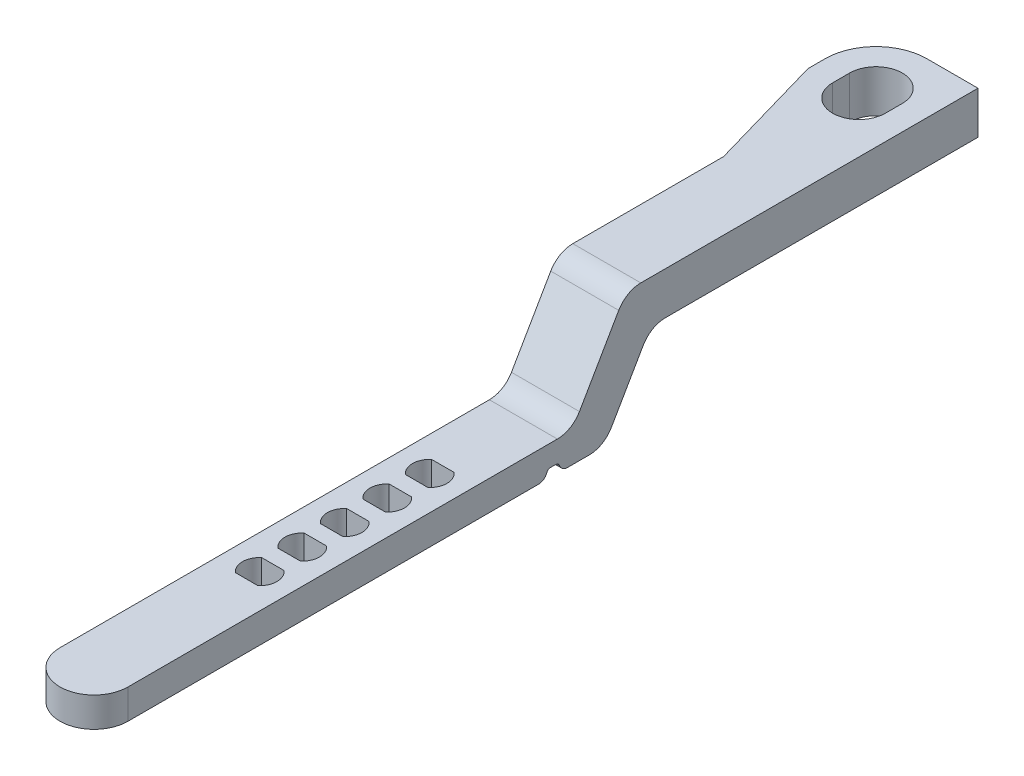
SolidWorks part; units mm, degrees
ref_plane "Front Plane" through (0, 0, 0) normal (0, 0, 1) x (1, 0, 0)
ref_plane "Top Plane" through (0, 0, 0) normal (0, 1, 0) x (1, 0, 0)
ref_plane "Right Plane" through (0, 0, 0) normal (1, 0, 0) x (0, 0, -1)
other "Configuration Table"
sketch "Sketch1" plane through (0, 0, 0) normal (0, 0, 1) x (1, 0, 0)
  line L1 (-4, 1.75) -> (4, 1.75)
  line L2 (-4, 1.75) -> (-4, -1.75)
  line L3 (-4, -1.75) -> (4, -1.75)
  line L4 (4, 1.75) -> (4, -1.75)
  line L5 (-4, 1.75) -> (4, -1.75) construction
  line L6 (-4, -1.75) -> (4, 1.75) construction
  point P0 (0, 0)
  dimension "D1" = 3.5
  dimension "D2" = 8
extrude "Base" add sketch "Sketch1" along normal blind 50
ref_plane "Plane1" through (0, 0, 50) normal (0, 0, 1) x (-1, 0, 0)
sketch "Sketch3" plane through (0, 0, 50) normal (0, 0, 1) x (-1, 0, 0)
  line L0 (-4, 1.75) -> (-4, -1.75) construction
  line L1 (-4, 1.75) -> (4, 1.75)
  line L2 (-4, 1.75) -> (-4, -1.75)
  line L3 (-4, -1.75) -> (4, -1.75)
  line L4 (4, 1.75) -> (4, -1.75)
  line L5 (-4, 1.75) -> (4, -1.75) construction
  line L6 (-4, -1.75) -> (4, 1.75) construction
  line L9 (4, -1.75) -> (4, 1.75) construction
  line L10 (-4, -1.75) -> (4, -1.75) construction
  line L11 (4, 1.75) -> (-4, 1.75) construction
  point P0 (0, 0)
extrude "Segment1" add sketch "Sketch3" along normal blind 50
ref_plane "Plane2" through (0, -17.0482, 96.6854) normal (0, -0.1736, 0.9848) x (-1, 0, 0)
sketch "Sketch5" plane through (0, -17.0482, 96.6854) normal (0, -0.1736, 0.9848) x (-1, 0, 0)
  line L0 (-4, -15.6414) -> (-4, -19.0882) construction
  line L1 (4, -19.0882) -> (-4, -19.0882)
  line L2 (4, -19.0882) -> (4, -15.6414)
  line L3 (4, -15.6414) -> (-4, -15.6414)
  line L4 (-4, -19.0882) -> (-4, -15.6414)
  line L5 (4, -15.6414) -> (-4, -15.6414) construction
extrude "Segment2" [suppressed] add sketch "Sketch5" along normal blind 1
sketch "Sketch12" plane through (0, 1.75, 0) normal (0, 1, 0) x (1, 0, 0)
  line L1 (-8, 0) -> (4, 0)
  line L2 (-8, 0) -> (-8, -7)
  line L3 (-8, -7) -> (4, -7)
  line L4 (4, 0) -> (4, -7)
  line L5 (-4, -100) -> (-4, 0) construction
  line L6 (4, 0) -> (-4, 0) construction
  line L7 (-8, -7) -> (-4, -21.9282)
  line L9 (-4, -7) -> (-4, -21.9282)
  line L11 (4, -100) -> (4, 0) construction
  line M6 (-4, 0) -> (-4, -100)
  line M8 (4, -100) -> (4, 0)
  dimension "D2" = 4
  dimension "D3" = 7
  dimension "D4" = 15
extrude "Boss-Extrude7" add sketch "Sketch12" against normal up to surface (3.5 mm away) contours L2 L3 L1 M6 | L4 L1 L3 M8 | L3 M8 | L3 L7 M6 region at (-6, 1.75, 3.5) region at (0, 1.75, 3.5) region at (-5.3333, 1.75, 11.9761) up to face at (0, -1.75, 50)
sketch "Sketch7" plane through (0, 1.75, 0) normal (0, 1, 0) x (1, 0, 0)
  line L0 (-1.925, -50) -> (1.925, -50) construction
  line L3 (-1.3226, -58.96) -> (1.3226, -58.96)
  line L4 (-1.3226, -62.04) -> (1.3226, -62.04)
  circle A0 centre (0, -60.5) radius 2.03
  point P2 (0, 0)
  dimension "D1" = 4.06
  dimension "D3" = 1.54
  dimension "D4" = 1.54
  dimension "D2" = 10.5
extrude "Hole_S1" [suppressed] cut sketch "Sketch7" against normal through all both and the other way through all
pattern_linear "LPattern_Hole_S1" [suppressed] of bodies 111
sketch "Sketch8" [suppressed] plane through (0, 15.378, 2.7116) normal (0, 0.9848, 0.1736) x (1, 0, 0)
  line L0 (4, -78.4807) -> (-4, -78.4807) construction
  line L1 (-1.3226, -87.4407) -> (1.3226, -87.4407)
  line L2 (-1.3226, -90.5207) -> (1.3226, -90.5207)
  circle A0 centre (0, -88.9807) radius 2.03
  dimension "D1" = 4.06
  dimension "D3" = 1.54
  dimension "D2" = 1.54
  dimension "D4" = 10.5
extrude "Hole_S2" [suppressed] cut sketch "Sketch8" against normal through all both and the other way through all contours L2 A0 L1
pattern_linear "LPattern_Hole_S2" [suppressed] of bodies 113
sketch "Sketch14" plane through (0, 1.75, 0) normal (0, 1, 0) x (1, 0, 0)
  line L0 (-4, -100) -> (-4, -21.9282) construction
  line L5 (4, -100) -> (4, 0) construction
  line L6 (4, -2) -> (4, -50)
  line L7 (4, -50) -> (-4, -50)
  line L8 (-4, -50) -> (-4, -21.9282)
  line L9 (-4, -21.9282) -> (-8, -8)
  line L12 (-8, -8) -> (-8, -6)
  line L13 (-8, 0) -> (-8, -7) construction
  line L14 (1.1, -6) -> (1.1, -8)
  line L16 (4, -100) -> (4, 0) construction
  line L18 (-5.1, -6) -> (-5.1, -8)
  line L19 (-1.925, -50) -> (1.925, -50) construction
  line L20 (4, 0) -> (-8, 0) construction
  line L22 (-2, 0) -> (0, 0)
  line L23 (0, 0) -> (4, -2)
  arc A0 (1.1, -8) -> (-5.1, -8) centre (-2, -8) cw
  circle A2 centre (-2, -6) radius 3.1
  arc A3 (-2, 0) -> (-8, -6) centre (-2, -6) ccw
  line M5 (4, 0) -> (-8, 0)
  line M6 (-4, -21.9282) -> (-4, -100)
  line M8 (4, -100) -> (4, 0)
  line M12 (-8, 0) -> (-8, -7)
  line M13 (-8, -7) -> (-4, -21.9282)
  dimension "D1" = 6.2
  dimension "D4" = 4
extrude "Boss-Extrude9" add sketch "Sketch14" along normal blind 11 contours L7 A2 L14 A0 L18 M8 M12 M13 M6 | L12 L9 M13 region at (-0.4988, 1.75, 25.1385) region at (-6.6667, 1.75, 12.3094)
extrude "Cut-Extrude10" cut sketch "Sketch14<2>" against normal through all both and the other way through all contours M5 M12 | M8 M5 | A2 | A2 L18 A0 L14 region at (2.6667, 1.75, 0.6667) region at (-6.6598, 1.75, 1.3402) region at (-2, 1.75, 6) region at (-2, 1.75, 9.4347)
sketch "Sketch14<2>" plane through (0, 1.75, 0) normal (0, 1, 0) x (1, 0, 0) same geometry as "Sketch14"
sketch "Sketch16" plane through (4, 0, 0) normal (1, 0, 0) x (0, 0, -1)
  line L0 (-50, 1.75) -> (-49.4848, 1.75)
  line L1 (-46.8868, 3.25) -> (-42.2679, 11.25)
  line L2 (0, 12.75) -> (0, -1.75) construction
  line L3 (-39.6699, 12.75) -> (0, 12.75)
  line L4 (0, 12.75) -> (0, 7.75)
  line L6 (0, 7.75) -> (-36.7831, 7.75)
  line L7 (-39.3812, 6.25) -> (-43.134, -0.25)
  line L8 (-100, -1.75) -> (-2, -1.75) construction
  line L9 (-45.7321, -1.75) -> (-50, -1.75)
  line L10 (-50, -1.75) -> (-50, 1.75)
  line L11 (0, 7.75) -> (0, -1.75)
  line L12 (0, -1.75) -> (-45.7321, -1.75)
  line L13 (-50, 1.75) -> (-50, 12.75)
  line L14 (-50, 12.75) -> (-39.6699, 12.75)
  line L16 (-50, 12.75) -> (-2, 12.75) construction
  arc A0 (-39.3812, 6.25) -> (-36.7831, 7.75) centre (-36.7831, 4.75) cw
  arc A1 (-42.2679, 11.25) -> (-39.6699, 12.75) centre (-39.6699, 9.75) cw
  arc A2 (-45.7321, -1.75) -> (-43.134, -0.25) centre (-45.7321, 1.25) ccw
  arc A3 (-49.4848, 1.75) -> (-46.8868, 3.25) centre (-49.4848, 4.75) ccw
  point P24 (-44, -1.75)
  line M20 (-100, -1.75) -> (-2, -1.75)
  line M23 (-50, 12.75) -> (-50, 1.75)
  dimension "D5" = 3
  dimension "D1" = 5
  dimension "D2" = 5
  dimension "D3" = 60
  dimension "D4" = 6
extrude "Cut-Extrude9" cut sketch "Sketch16" against normal through all both and the other way through all contours L0 A3 L1 A1 M23 | A2 L6 A0 L7 M20 | L12 L11 L6 region at (4, 8.4077, 46.9243) region at (4, 2.8838, 20.6664)
sketch "Sketch18" [suppressed] plane through (0, 15.378, 2.7116) normal (0, 0.9848, 0.1736) x (1, 0, 0)
  line L0 (4, -113.4807) -> (-4, -113.4807) construction
  line L1 (4, -113.4807) -> (-4, -113.4807)
  arc A0 (4, -113.4807) -> (-4, -113.4807) centre (0, -113.4807) cw
extrude "Boss-Extrude11" [suppressed] add sketch "Sketch18" against normal up to surface (3.4468 mm away)
sketch "Sketch19" [suppressed] plane through (-4, 0, 0) normal (-1, 0, 0) x (0, 0, 1)
  line L0 (80, -1.75) -> (40.7321, -1.75) construction
  line L5 (80, -1.75) -> (40.7321, -1.75) construction
  line L6 (44.4848, 1.75) -> (44.4848, -1.75) construction
  line L7 (80, -1.75) -> (40.7321, -1.75) construction
  line L9 (113.8697, -7.7221) -> (80, -1.75) construction
  line L12 (44.5629, 0.25) -> (45.4068, 0.25)
  line L13 (44.093, -0.079) -> (43.4848, -1.75)
  line L14 (43.4848, -1.75) -> (46.4848, -1.75)
  line L15 (45.8766, -0.079) -> (46.4848, -1.75)
  line L16 (79.1025, -0.079) -> (78.4943, -1.75)
  line L18 (81.1741, -0.2602) -> (81.4829, -2.0115)
  line L19 (113.8697, -7.7221) -> (80, -1.75) construction
  line L20 (78.4943, -1.75) -> (80, -1.75)
  line L22 (79.5723, 0.25) -> (80.175, 0.25)
  line L23 (80.7685, 0.1453) -> (80.175, 0.25)
  line L24 (81.4829, -2.0115) -> (80, -1.75)
  arc A3 (45.8766, -0.079) -> (45.4068, 0.25) centre (45.4068, -0.25) ccw
  arc A4 (44.093, -0.079) -> (44.5629, 0.25) centre (44.5629, -0.25) cw
  arc A7 (81.1741, -0.2602) -> (80.7685, 0.1453) centre (80.6817, -0.3471) ccw
  arc A8 (79.1025, -0.079) -> (79.5723, 0.25) centre (79.5723, -0.25) cw
  point P11 (80, -1.75)
  point P13 (80.175, 0.25)
  point P40 (44.9848, -1.75)
  point P43 (44.9848, -1.75)
  dimension "D3" = 0.5
  dimension "D6" = 70
  dimension "D12" = 0.5
  dimension "D17" = 3
  dimension "D1" = 0
  dimension "D2" = 2
  dimension "D4" = 3
  dimension "D5" = 70
  dimension "D8" = 70
  dimension "D9" = 70
  dimension "D10" = 0.5
  dimension "D16" = 2
extrude "Cut-Extrude11" [suppressed] cut sketch "Sketch19" against normal blind 10
sketch "Sketch22" plane through (0, 1.75, 0) normal (0, 1, 0) x (1, 0, 0)
  line L0 (-4, -100) -> (4, -100)
  arc A0 (-4, -100) -> (4, -100) centre (0, -100) ccw
extrude "Boss-Extrude13" add sketch "Sketch22" against normal up to surface (3.5 mm away) up to face at (0, -1.75, 72.866)
sketch "Sketch23" plane through (-4, 0, 0) normal (-1, 0, 0) x (0, 0, 1)
  line L12 (49.6989, -0.75) -> (50.2708, -0.75)
  line L13 (49.2291, -1.079) -> (48.9848, -1.75)
  line L14 (48.9848, -1.75) -> (50.9848, -1.75)
  line L15 (50.7406, -1.079) -> (50.9848, -1.75)
  line L25 (100, -1.75) -> (45.7321, -1.75) construction
  line L27 (49.4848, 1.75) -> (49.4848, -1.75) construction
  arc A3 (50.7406, -1.079) -> (50.2708, -0.75) centre (50.2708, -1.25) ccw
  arc A4 (49.2291, -1.079) -> (49.6989, -0.75) centre (49.6989, -1.25) cw
  point P40 (49.9848, -1.75)
  point P43 (49.9848, -1.75)
  dimension "D3" = 0.5
  dimension "D17" = 2
  dimension "D2" = 1
  dimension "D8" = 70
  dimension "D9" = 70
  dimension "D10" = 0.5
  dimension "D18" = 0
extrude "Cut-Extrude12" cut sketch "Sketch23" against normal blind 10
sketch "Sketch24" plane through (0, 1.75, 0) normal (0, 1, 0) x (1, 0, 0)
  line L1 (-1.925, -50) -> (1.925, -50) construction
  line L3 (-1.3226, -58.96) -> (1.3226, -58.96)
  line L4 (-1.3226, -62.04) -> (1.3226, -62.04)
  circle A0 centre (0, -60.5) radius 2.03
  point P2 (0, -23.7142)
  dimension "D1" = 4.06
  dimension "D2" = 10.5
  dimension "D3" = 1.54
  dimension "D4" = 1.54
extrude "Cut-Extrude13" cut sketch "Sketch24" against normal through all both and the other way through all contours L4 A0 L3 region at (0, 1.75, 60.5)
pattern_linear "LPattern3" count 5 spacing 5 along (0, 0, 1) of "Cut-Extrude13"
sketch "Sketch25" plane through (0, 12.75, 0) normal (0, 1, 0) x (1, 0, 0)
  line L0 (4, -2) -> (4, 0)
  line L1 (4, 0) -> (0, 0)
  line L2 (0, 0) -> (4, -2) construction
  line L3 (0, 0) -> (4, -2)
extrude "Boss-Extrude14" add sketch "Sketch25" against normal up to surface (5 mm away) up to face at (-2, 7.75, 7)
fillet "Fillet4" [suppressed] radius 1
fillet "Fillet5" radius 1 2 edges at (0, -1.75, 48.9848) (0, -1.75, 50.9848)
equation "\"LF\" = 0.06mm"
equation "\"TF\" = 0.04mm"
equation "\"PF\" = 0.1mm"
equation "\"AngLF\" = 0.05deg"
equation "\"AngTF\" = 0.02deg"
equation "\"D1@Sketch7\"=4+\"LF\""
equation "\"D4@Sketch7\"=1.5+\"TF\""
equation "\"D3@Sketch7\"=1.5+\"TF\""
equation "\"D1@Sketch8\"=4+\"LF\""
equation "\"D3@Sketch8\"=1.5+\"TF\""
equation "\"D1@Sketch14\"=6+2*\"PF\""
